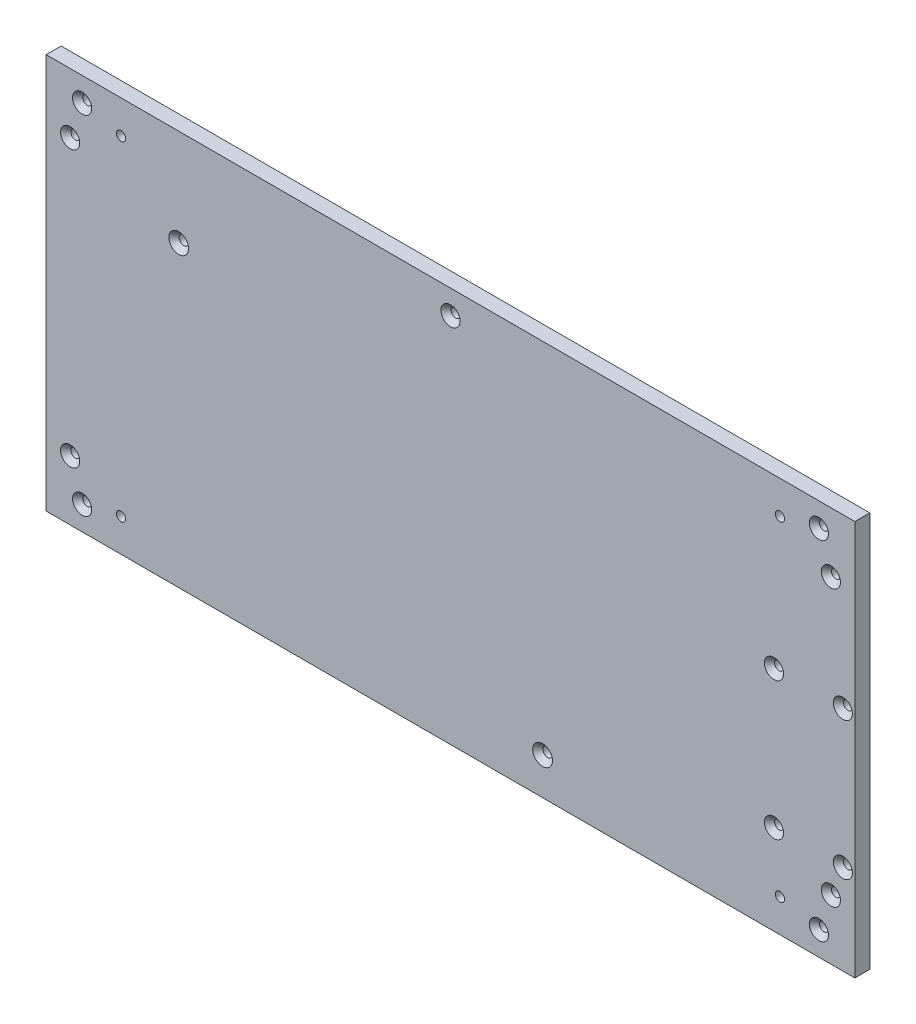
SolidWorks part; units mm, degrees
ref_plane "Front Plane" through (0, 0, 0) normal (0, 0, 1) x (1, 0, 0)
ref_plane "Top Plane" through (0, 0, 0) normal (0, 1, 0) x (1, 0, 0)
ref_plane "Right Plane" through (0, 0, 0) normal (1, 0, 0) x (0, 0, -1)
sketch "Sketch1" plane through (0, 0, 0) normal (0, 0, 1) x (1, 0, 0)
  line L1 (135, -66) -> (-135, -66)
  line L2 (135, -66) -> (135, 66)
  line L3 (135, 66) -> (-135, 66)
  line L4 (-135, -66) -> (-135, 66)
  line L5 (135, -66) -> (-135, 66) construction
  line L6 (135, 66) -> (-135, -66) construction
  point P0 (0, 0)
  dimension "D1" = 270
  dimension "D2" = 132
extrude "Base" add sketch "Sketch1" along normal mid plane 5 contours L4 L1 L2 L3 region at (0, 0, 0)
sketch "Sketch2" plane through (0, 0, 2.5) normal (0, 0, 1) x (1, 0, 0)
  line L0 (135, 66) -> (-135, 66) construction
  line L1 (135, -66) -> (135, 66) construction
  line L2 (-135, -66) -> (-135, 66) construction
  line L3 (135, -66) -> (-135, -66) construction
  circle A0 centre (-127, -46) radius 1.5
  circle A1 centre (-123, -58) radius 1.5
  circle A2 centre (-127, 46) radius 1.5
  circle A3 centre (-123, 58) radius 1.5
  circle A5 centre (0, 58) radius 1.5
  circle A6 centre (123, -58) radius 1.5
  circle A7 centre (127, -46) radius 1.5
  circle A8 centre (127, 46) radius 1.5
  circle A9 centre (123, 58) radius 1.5
  dimension "D5" = 8
  dimension "D10" = 3
  dimension "D2" = 8
  dimension "D3" = 12
  dimension "D4" = 12
  dimension "D6" = 20
  dimension "D7" = 20
  dimension "D8" = 8
  dimension "D9" = 8
extrude "FastenersHoles" cut sketch "Sketch2" against normal through all
sketch "Sketch3" plane through (0, 0, -2.5) normal (0, 0, -1) x (-1, 0, 0)
  line L3 (90.75, -53.65) -> (-30.75, -53.65) construction
  line L4 (90.75, -53.65) -> (90.75, 33.65) construction
  line L5 (90.75, 33.65) -> (-30.75, 33.65) construction
  line L6 (-30.75, -53.65) -> (-30.75, 33.65) construction
  line L7 (90.75, -53.65) -> (-30.75, 33.65) construction
  line L8 (90.75, 33.65) -> (-30.75, -53.65) construction
  circle A0 centre (-30.75, -53.65) radius 1.6
  circle A1 centre (90.75, 33.65) radius 1.6
  point P2 (30, -10)
  dimension "D3" = 3.2
  dimension "D1" = 121.5
  dimension "D2" = 87.3
  dimension "D4" = 10
  dimension "D5" = 30
extrude "PSUMount" cut sketch "Sketch3" against normal through all
sketch "Sketch4" plane through (0, 0, 2.5) normal (0, 0, 1) x (1, 0, 0)
  line L1 (131, 10) -> (108, 10) construction
  line L2 (131, 10) -> (131, -36) construction
  line L3 (131, -36) -> (108, -36) construction
  line L4 (108, 10) -> (108, -36) construction
  line L5 (131, 10) -> (108, -36) construction
  line L6 (131, -36) -> (108, 10) construction
  line L7 (135, -66) -> (135, 66) construction
  circle A0 centre (108, 10) radius 1.5
  circle A1 centre (131, 10) radius 1.5
  circle A2 centre (108, -36) radius 1.5
  circle A3 centre (131, -36) radius 1.5
  point P0 (119.5, -13)
  point P16 (135, 0)
  dimension "D5" = 3
  dimension "D1" = 46
  dimension "D2" = 23
  dimension "D3" = 4
  dimension "D4" = 13
extrude "InterfaceHoles" cut sketch "Sketch4" against normal through all
chamfer "ChamferAll" distance 1.7 angle 45 15 edges at (29.15, -53.65, 2.5) (-121.5, -58, 2.5) (-125.5, -46, 2.5) (-121.5, 58, 2.5) (-125.5, 46, 2.5) (-92.35, 33.65, 2.5) (1.5, 58, 2.5) (124.5, 58, 2.5) (128.5, 46, 2.5) (128.5, -46, 2.5) (124.5, -58, 2.5) (132.5, 10, 2.5) (132.5, -36, 2.5) (109.5, -36, 2.5) (109.5, 10, 2.5)
sketch "Sketch5" plane through (0, 0, 2.5) normal (0, 0, 1) x (1, 0, 0)
  line L1 (110, -55) -> (-110, -55) construction
  line L2 (110, -55) -> (110, 55) construction
  line L3 (110, 55) -> (-110, 55) construction
  line L4 (-110, -55) -> (-110, 55) construction
  line L5 (110, -55) -> (-110, 55) construction
  line L6 (110, 55) -> (-110, -55) construction
  circle A0 centre (-110, -55) radius 1.55
  circle A1 centre (-110, 55) radius 1.55
  circle A2 centre (110, 55) radius 1.55
  circle A3 centre (110, -55) radius 1.55
  point P8 (0, 0)
  dimension "D1" = 3.1
  dimension "D2" = 110
  dimension "D3" = 220
extrude "Cut-Extrude2" cut sketch "Sketch5" against normal through all
